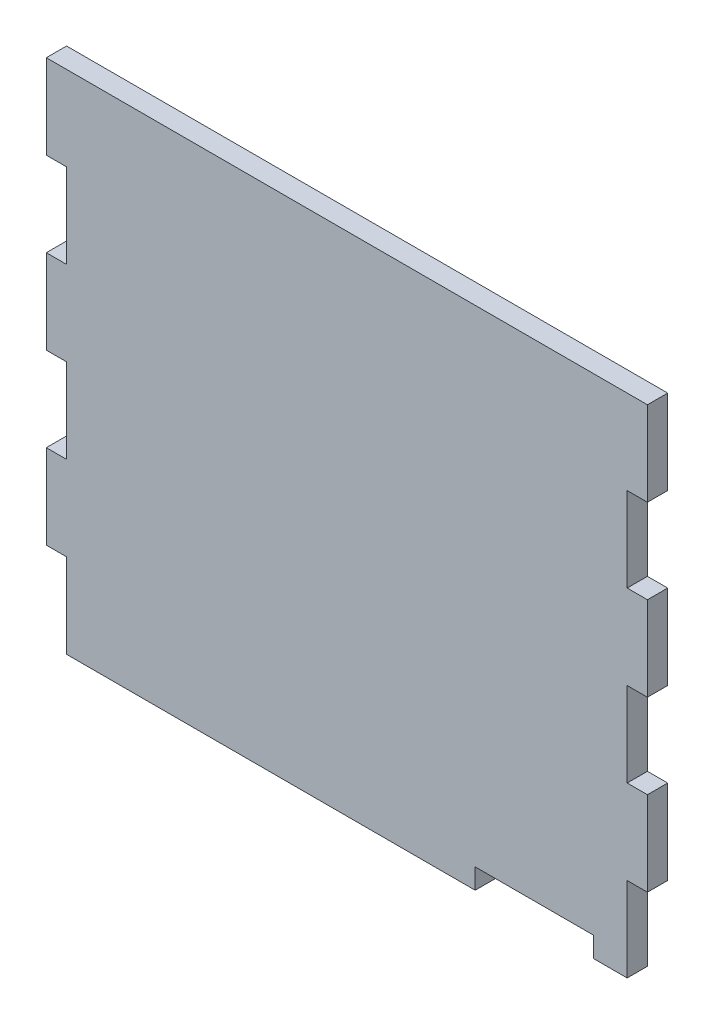
SolidWorks part; units mm, degrees
ref_plane "Front" through (0, 0, 0) normal (0, 0, 1) x (1, 0, 0)
ref_plane "Top" through (0, 0, 0) normal (0, 1, 0) x (1, 0, 0)
ref_plane "Right" through (0, 0, 0) normal (1, 0, 0) x (0, 0, -1)
sketch "Sketch1" plane through (0, 0, 0) normal (0, 0, 1) x (1, 0, 0)
  line L1 (0, 0) -> (-178, 0)
  line L2 (0, 0) -> (0, 150)
  line L3 (0, 150) -> (-178, 150)
  line L4 (-178, 0) -> (-178, 150)
  dimension "D1" = 150
  dimension "D2" = 178
extrude "Boss-Extrude1" add sketch "Sketch1" along normal blind 6
sketch "Sketch2" plane through (0, 0, 6) normal (0, 0, 1) x (1, 0, 0)
  line L0 (-178, 150) -> (-178, 0) construction
  line L1 (-178, 125) -> (-172, 125)
  line L2 (-178, 125) -> (-178, 100)
  line L3 (-178, 100) -> (-172, 100)
  line L4 (-172, 125) -> (-172, 100)
  line L5 (0, 150) -> (-178, 150) construction
  dimension "D1" = 25
  dimension "D2" = 25
  dimension "D3" = 6
extrude "Cut-Extrude1" cut sketch "Sketch2" against normal blind 6
pattern_linear "LPattern1" count 3 spacing 50 along (0, -1, 0) count 2 spacing 172 along (1, 0, 0) of "Cut-Extrude1"
sketch "Sketch3" plane through (0, 0, 6) normal (0, 0, 1) x (1, 0, 0)
  line L0 (-172, 0) -> (-6, 0) construction
  line L1 (-16, 0) -> (-51, 0)
  line L2 (-16, 0) -> (-16, 6)
  line L3 (-16, 6) -> (-51, 6)
  line L4 (-51, 0) -> (-51, 6)
  line L6 (-6, 25) -> (-6, 0) construction
  point P6 (-6, 0)
  dimension "D1" = 35
  dimension "D2" = 10
  dimension "D3" = 6
extrude "Cut-Extrude2" cut sketch "Sketch3" against normal through all
